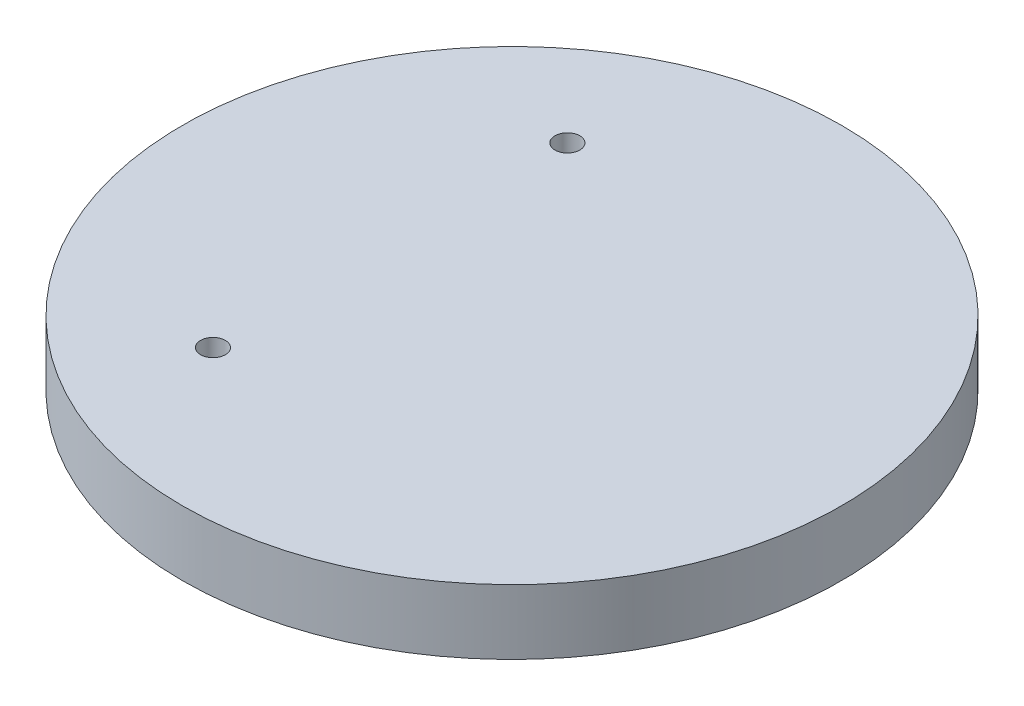
SolidWorks part; units mm, degrees
ref_plane "Front Plane" through (0, 0, 0) normal (0, 0, 1) x (1, 0, 0)
ref_plane "Top Plane" through (0, 0, 0) normal (0, 1, 0) x (1, 0, 0)
ref_plane "Right Plane" through (0, 0, 0) normal (1, 0, 0) x (0, 0, -1)
sketch "Sketch2" plane through (0, 0, 0) normal (0, 0, 1) x (1, 0, 0)
  line L0 (0, 0) -> (0, 6) construction
  line L1 (0, 4) -> (-3.05, 4)
  line L2 (-3.05, 3) -> (-3.05, 0)
  line L3 (-3.05, 0) -> (-5.05, 0)
  line L4 (-5.05, 0) -> (-5.05, 4)
  line L5 (-5.05, 4) -> (-28.5, 4)
  line L6 (-28.5, 4) -> (-28.5, 0)
  line L7 (-28.5, 0) -> (-30.5, 0)
  line L8 (-30.5, 0) -> (-30.5, 4)
  line L9 (-30.5, 4) -> (-30.5, 6)
  line L10 (-30.5, 6) -> (0, 6)
  line L11 (-3.05, 4) -> (-3.05, 3)
  line L12 (0, 6) -> (0, 4)
  point P13 (-5.05, 2)
  dimension "D1" = 6
  dimension "D2" = 30.5
  dimension "D3" = 3.05
  dimension "D4" = 2
  dimension "D5" = 2
  dimension "D6" = 4
  dimension "D7" = 6
  dimension "D8" = 2
  dimension "D9" = 2
revolve "Revolve1" add sketch "Sketch2" angle 360 about L0
fillet "Fillet1" radius 10 2 edges at (0, 4, -5.05) (0, 4, -28.5)
sketch "Sketch6" plane through (0, 6, 0) normal (0, 1, 0) x (1, 0, 0)
  line L0 (-22.55, -13.4) -> (0, -19.4)
  line L1 (-22.55, -11.4) -> (0, -11.4)
  line L2 (-22.55, -11.4) -> (-22.55, 11.4)
  line L3 (-22.55, 11.4) -> (0, 11.4)
  line L4 (0, -11.4) -> (0, 11.4)
  line L5 (-22.55, -11.4) -> (0, 11.4) construction
  line L6 (-22.55, 11.4) -> (0, -11.4) construction
  line L7 (-22.55, -11.4) -> (0, -11.4)
  line L8 (-22.55, -11.4) -> (-22.55, -19.4)
  line L9 (-22.55, -19.4) -> (0, -19.4)
  line L10 (0, -11.4) -> (0, -19.4)
  line L11 (-22.55, 11.4) -> (0, 11.4)
  line L12 (-22.55, 11.4) -> (-22.55, 19.4)
  line L13 (-22.55, 19.4) -> (0, 19.4)
  line L14 (0, 11.4) -> (0, 19.4)
  line L15 (-22.55, 11.4) -> (0, 11.4)
  line L16 (-22.55, 11.4) -> (-22.55, 13.4)
  line L17 (-22.55, 13.4) -> (0, 13.4)
  line L18 (0, 11.4) -> (0, 13.4)
  line L19 (-22.55, -11.4) -> (0, -11.4)
  line L20 (-22.55, -11.4) -> (-22.55, -13.4)
  line L21 (-22.55, -13.4) -> (0, -13.4)
  line L22 (0, -11.4) -> (0, -13.4)
  line L23 (-22.55, -19.4) -> (0, -13.4)
  line L24 (-22.55, 19.4) -> (0, 13.4)
  line L25 (-22.55, 13.4) -> (0, 19.4)
  circle A0 centre (-11.275, 16.4) radius 1.15
  circle A1 centre (-11.275, -16.4) radius 1.15
  point P0 (-11.275, 0)
  dimension "D1" = 22.8
  dimension "D2" = 22.55
  dimension "D3" = 0
  dimension "D4" = 11.4
  dimension "D5" = 8
  dimension "D6" = 8
  dimension "D7" = 2
  dimension "D8" = 2
extrude "Cut-Extrude1" cut sketch "Sketch6" against normal blind 10 contours A1 | A0
